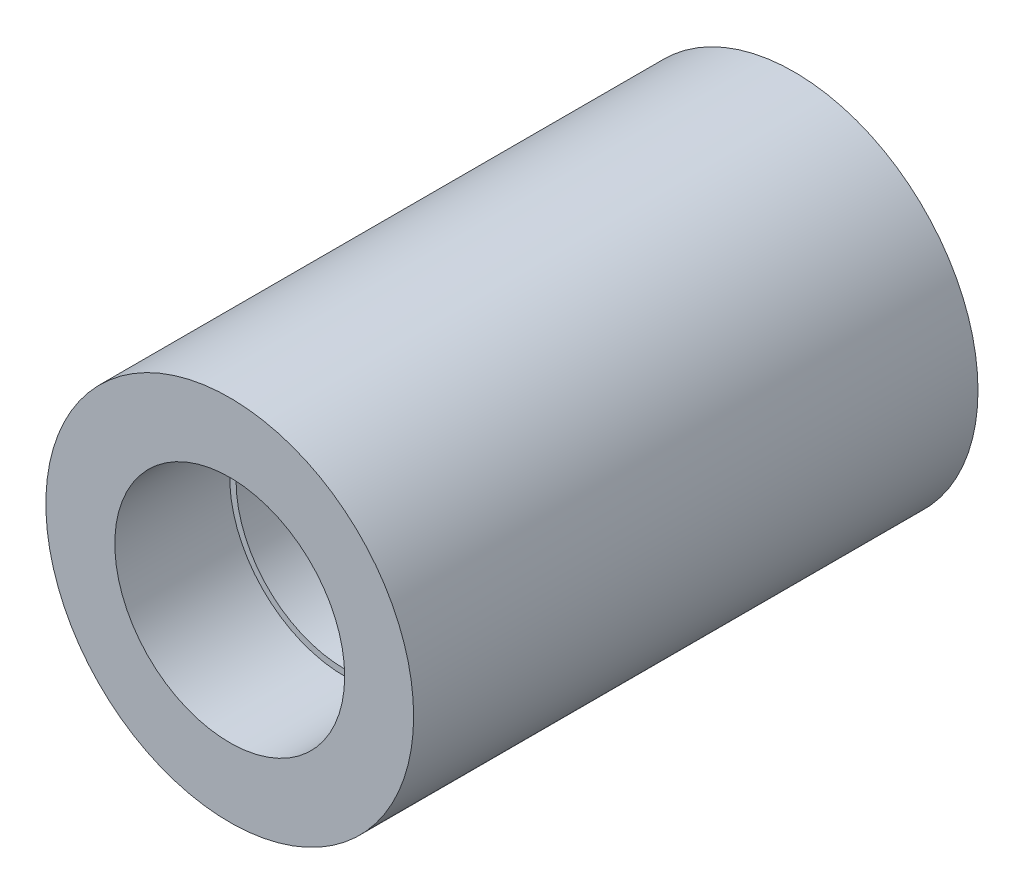
SolidWorks part; units mm, degrees
material "PLA"
ref_plane "Front Plane" through (0, 0, 0) normal (0, 0, 1) x (1, 0, 0)
ref_plane "Top Plane" through (0, 0, 0) normal (0, 1, 0) x (1, 0, 0)
ref_plane "Right Plane" through (0, 0, 0) normal (1, 0, 0) x (0, 0, -1)
sketch "Sketch1" plane through (0, 0, 0) normal (0, 0, 1) x (1, 0, 0)
  circle A0 centre (0, 0) radius 3.175
  circle A1 centre (0, 0) radius 5.08
  circle A2 centre (0, 0) radius 3
  dimension "D1" = 6.35
  dimension "D2" = 10.16
  dimension "D3" = 6
extrude "Boss-Extrude1" add sketch "Sketch1" along normal blind 3.175 contours A1 A0 region at (-4.9363, 0, 0)
extrude "Boss-Extrude2" add sketch "Sketch1<3>" against normal blind 12.4155 contours A1 A0 | A0 A2 region at (-3.0852, 0, 0) region at (-4.9363, 0, 0)
sketch "Sketch1<3>" plane through (0, 0, 0) normal (0, 0, 1) x (1, 0, 0) same geometry as "Sketch1"
